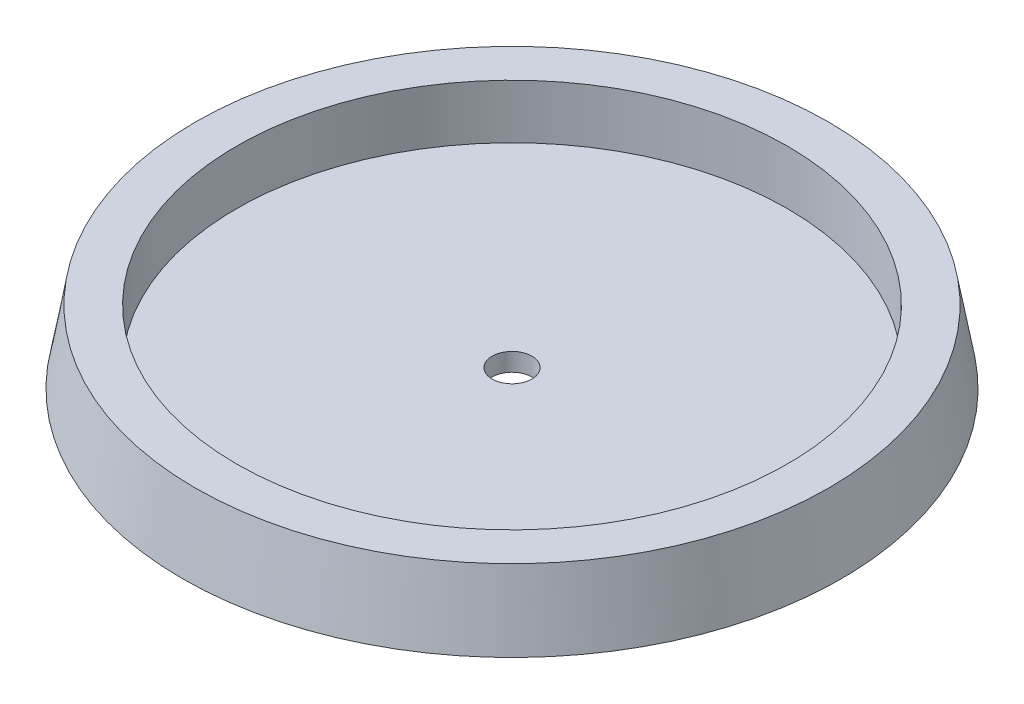
SolidWorks part; units mm, degrees
ref_plane "Front Plane" through (0, 0, 0) normal (0, 0, 1) x (1, 0, 0)
ref_plane "Top Plane" through (0, 0, 0) normal (0, 1, 0) x (1, 0, 0)
ref_plane "Right Plane" through (0, 0, 0) normal (1, 0, 0) x (0, 0, -1)
sketch "Sketch1" plane through (0, 0, 0) normal (0, 1, 0) x (1, 0, 0)
  circle A0 centre (0, 0) radius 15.25
  circle A2 centre (0, 0) radius 18.25
  circle A4 centre (0, 0) radius 1.1
  point P13 (0, 0)
  dimension "D1" = 30.5
  dimension "D4" = 36.5
  dimension "D6" = 2.2
extrude "Boss-Extrude1" add sketch "Sketch1" along normal blind 4 draft 10 contours A2 A0 | A0 | A0 | A2 A0 | A2 | A2 | A2 | A2 | A2 | A4 region at (-14.8187, 0, 0) region at (-17.7338, 0, 0) region at (0, 0, 0)
extrude "Cut-Extrude2" cut sketch "Sketch1<5>" against normal blind 4 from surface contours A4 region at (0, 0, 0) starting at face at (0, 4, 17.5447)
sketch "Sketch1<5>" plane through (0, 0, 0) normal (0, 1, 0) x (1, 0, 0) same geometry as "Sketch1"
extrude "Cut-Extrude3" cut sketch "Sketch1<6>" against normal blind 3 from surface contours A0 A4 region at (-14.8187, 0, 0) starting at face at (0, 4, 1.1)
sketch "Sketch1<6>" plane through (0, 0, 0) normal (0, 1, 0) x (1, 0, 0) same geometry as "Sketch1"
